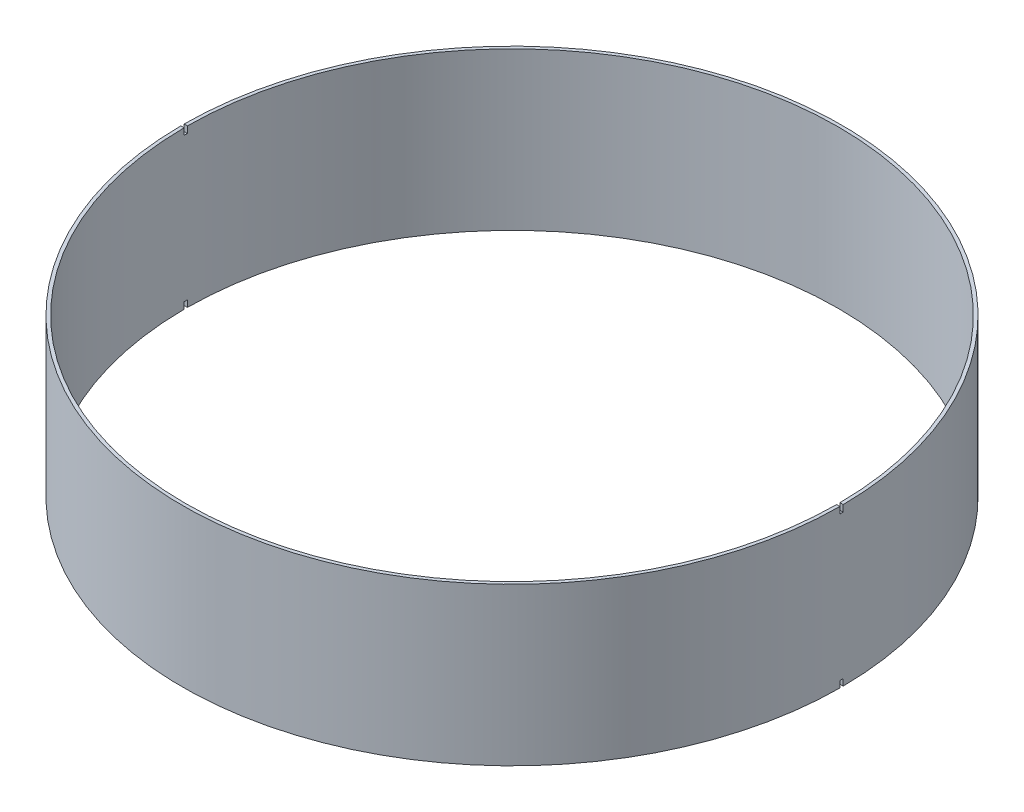
SolidWorks part; units mm, degrees
ref_plane "Front Plane" through (0, 0, 0) normal (0, 0, 1) x (1, 0, 0)
ref_plane "Top Plane" through (0, 0, 0) normal (0, 1, 0) x (1, 0, 0)
ref_plane "Right Plane" through (0, 0, 0) normal (1, 0, 0) x (0, 0, -1)
sketch "Эскиз1" plane through (0, 0, 0) normal (0, 1, 0) x (1, 0, 0)
  circle A0 centre (0, 0) radius 50.3
  circle A1 centre (0, 0) radius 49.8
extrude "Бобышка-Вытянуть1" add sketch "Эскиз1" along normal blind 24
sketch "Эскиз3" plane through (0, 0, 0) normal (1, 0, 0) x (0, 0, -1)
  line L0 (0, 24) -> (0.25, 24)
  line L8 (0, 24) -> (-0.25, 24)
  line L9 (-0.25, 24) -> (-0.25, 23)
  line L10 (-0.25, 23) -> (0.25, 23)
  line L11 (0.25, 23) -> (0.25, 24)
  line L12 (0, 0) -> (0, 24) construction
  line L14 (0, 12) -> (3.0275, 12) construction
  line L15 (0.25, 1) -> (0.25, 0)
  line L16 (-0.25, 1) -> (0.25, 1)
  line L17 (-0.25, 0) -> (-0.25, 1)
  line L18 (0, 0) -> (-0.25, 0)
  line L19 (0, 0) -> (0.25, 0)
extrude "Вырез-Вытянуть2" cut sketch "Эскиз3" against normal blind 52 and the other way blind 52
